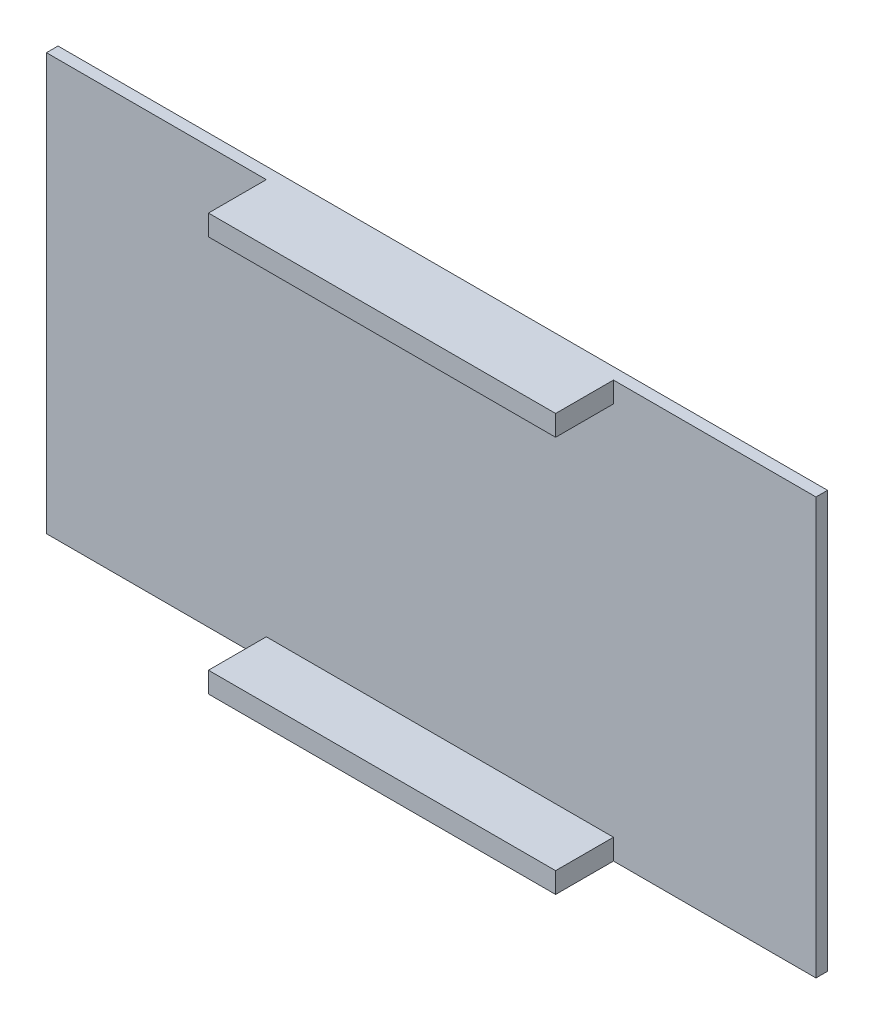
SolidWorks part; units mm, degrees
ref_plane "Front Plane" through (0, 0, 0) normal (0, 0, 1) x (1, 0, 0)
ref_plane "Top Plane" through (0, 0, 0) normal (0, 1, 0) x (1, 0, 0)
ref_plane "Right Plane" through (0, 0, 0) normal (1, 0, 0) x (0, 0, -1)
sketch "Sketch1" plane through (0, 0, 0) normal (0, 0, 1) x (1, 0, 0)
  line L1 (-66.5, -36) -> (66.5, -36)
  line L2 (-66.5, -36) -> (-66.5, 36)
  line L3 (-66.5, 36) -> (66.5, 36)
  line L4 (66.5, -36) -> (66.5, 36)
  line L5 (-66.5, -36) -> (66.5, 36) construction
  line L6 (-66.5, 36) -> (66.5, -36) construction
  point P0 (0, 0)
  dimension "D1" = 72
  dimension "D2" = 133
extrude "Boss-Extrude1" add sketch "Sketch1" along normal blind 2
sketch "Sketch2" plane through (0, 0, 2) normal (0, 0, 1) x (1, 0, 0)
  line L0 (-28.5, 36) -> (31.5, 36)
  line L1 (-28.5, 36) -> (-28.5, 32.4298)
  line L2 (31.5, 36) -> (31.5, 32.4298)
  line L3 (-28.5, 32.4298) -> (31.5, 32.4298)
  line L4 (66.5, 36) -> (-66.5, 36) construction
  line L5 (66.5, -36) -> (66.5, 36) construction
  dimension "D1" = 60
  dimension "D2" = 35
extrude "Boss-Extrude2" add sketch "Sketch2" along normal blind 10
ref_point "Point1"
ref_axis "Axis1" through (-66.5, 0, 1) along (-1, 0, 0)
ref_plane "Plane1" through (0, 0, 0) normal (0, 1, 0) x (-1, 0, 0)
mirror "Mirror1" about plane through (0, 0, 0) normal (0, 1, 0) of "Boss-Extrude2"
